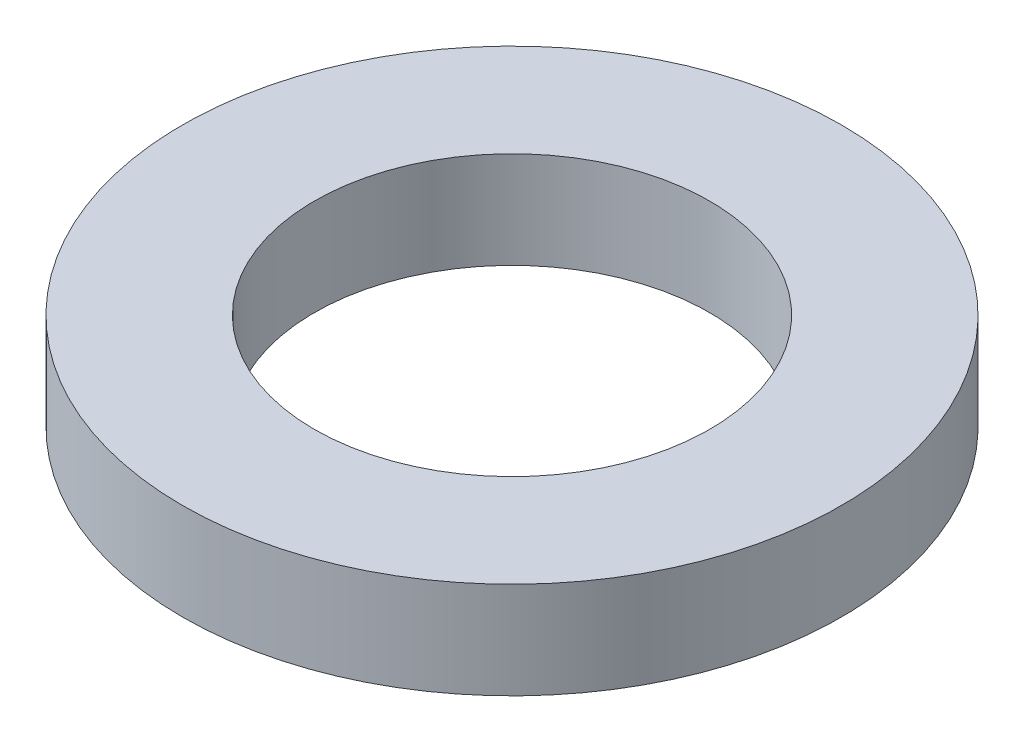
SolidWorks part; units mm, degrees
ref_plane "Front Plane" through (0, 0, 0) normal (0, 0, 1) x (1, 0, 0)
ref_plane "Top Plane" through (0, 0, 0) normal (0, 1, 0) x (1, 0, 0)
ref_plane "Right Plane" through (0, 0, 0) normal (1, 0, 0) x (0, 0, -1)
sketch "Sketch1" plane through (0, 0, 0) normal (0, 1, 0) x (1, 0, 0)
  circle A0 centre (0, 0) radius 75
  dimension "FLANGE_OD" = 150
extrude "Boss-Extrude1" add sketch "Sketch1" along normal blind 22
sketch "Sketch2" plane through (0, 0, 0) normal (0, 1, 0) x (1, 0, 0)
  circle A0 centre (0, 0) radius 45
  dimension "BORE_D" = 90
extrude "Cut-Extrude1" cut sketch "Sketch2" along normal through all
sketch "Sketch3" plane through (0, 22, 0) normal (0, 1, 0) x (1, 0, 0)
  circle A0 centre (0, 0) radius 27.3017 construction
  circle A1 centre (-27.3017, 0) radius 2.123
  dimension "BOLT_D" = 4.246
  dimension "BOLT_PCD" = 54.6035
extrude "Cut-Extrude2" cut sketch "Sketch3" against normal blind 20.2591 rebuild error yes
pattern_circular "CirPattern1" count 6 over 360 rebuild error yes
